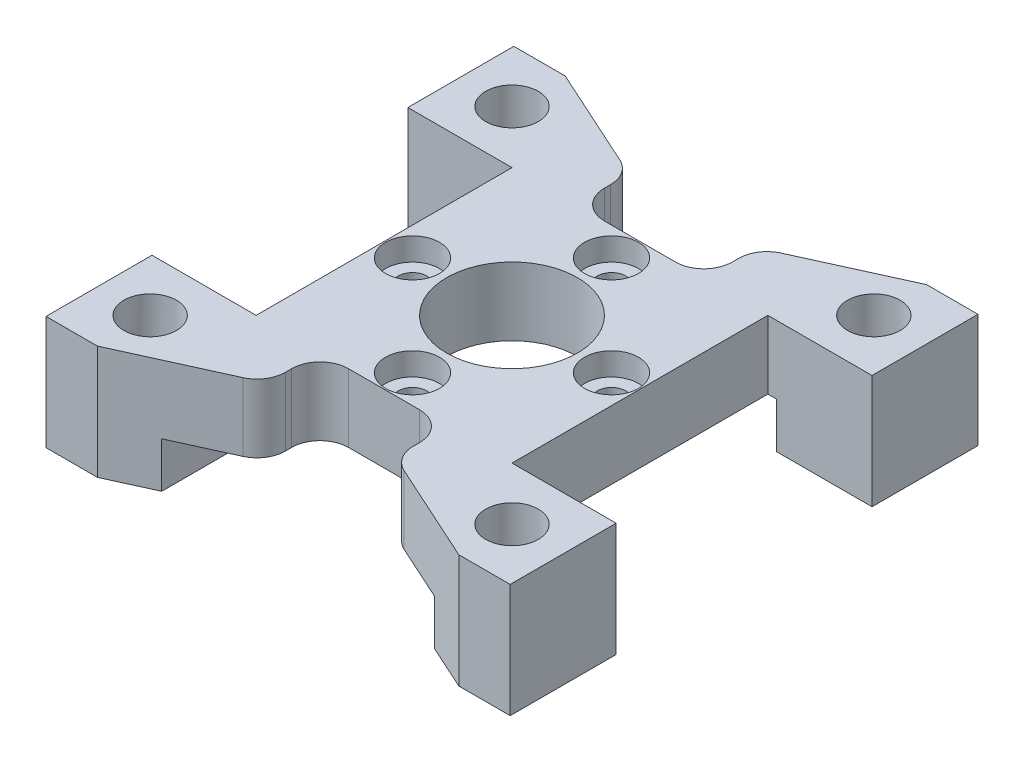
SolidWorks part; units mm, degrees
ref_plane "Front Plane" through (0, 0, 0) normal (0, 0, 1) x (1, 0, 0)
ref_plane "Top Plane" through (0, 0, 0) normal (0, 1, 0) x (1, 0, 0)
ref_plane "Right Plane" through (0, 0, 0) normal (1, 0, 0) x (0, 0, -1)
sketch "Sketch1" plane through (0, 0, 0) normal (0, 1, 0) x (1, 0, 0)
  line L0 (-31.8198, 31.8198) -> (0, 0) construction
  line L1 (-22.5, -22.5) -> (22.5, -22.5)
  line L2 (-22.5, -22.5) -> (-22.5, 22.5)
  line L3 (-22.5, 22.5) -> (22.5, 22.5)
  line L4 (22.5, -22.5) -> (22.5, 22.5)
  line L5 (-22.5, -22.5) -> (22.5, 22.5) construction
  line L6 (-22.5, 22.5) -> (22.5, -22.5) construction
  line L15 (0, 22.5) -> (0, -22.5) construction
  line L16 (0, 0) -> (31.8198, -31.8198) construction
  line L17 (-22.5, 0) -> (22.5, 0) construction
  line L18 (11.25, 22.5) -> (40.8198, 22.5)
  line L19 (11.25, 22.5) -> (11.25, 31.8198)
  line L20 (31.7885, 41.1398) -> (40.8198, 41.1398)
  line L21 (40.8198, 22.5) -> (40.8198, 41.1398)
  line L22 (0, 22.5) -> (22.5, 22.5) construction
  line L23 (11.25, 31.8198) -> (31.7885, 41.1398)
  line L24 (-40.8198, 22.5) -> (-40.8198, 41.1398)
  line L25 (-31.7885, 41.1398) -> (-40.8198, 41.1398)
  line L26 (-11.25, 31.8198) -> (-31.7885, 41.1398)
  line L27 (-11.25, 22.5) -> (-11.25, 31.8198)
  line L28 (-11.25, 22.5) -> (-40.8198, 22.5)
  line L29 (11.25, -22.5) -> (40.8198, -22.5)
  line L30 (40.8198, -22.5) -> (40.8198, -41.1398)
  line L31 (31.7885, -41.1398) -> (40.8198, -41.1398)
  line L32 (11.25, -31.8198) -> (31.7885, -41.1398)
  line L33 (11.25, -22.5) -> (11.25, -31.8198)
  line L34 (-11.25, -22.5) -> (-11.25, -31.8198)
  line L35 (-11.25, -22.5) -> (-40.8198, -22.5)
  line L36 (-40.8198, -22.5) -> (-40.8198, -41.1398)
  line L37 (-31.7885, -41.1398) -> (-40.8198, -41.1398)
  line L38 (-11.25, -31.8198) -> (-31.7885, -41.1398)
  line L44 (24, -37.6055) -> (-24, -37.6055)
  line L45 (24, -37.6055) -> (24, 37.6055)
  line L46 (24, 37.6055) -> (-24, 37.6055)
  line L47 (-24, -37.6055) -> (-24, 37.6055)
  point P0 (0, 0)
  point P6 (-31.8198, 31.8198)
  point P14 (31.8198, 31.8198)
  point P15 (31.8198, -31.8198)
  point P16 (-31.8198, -31.8198)
  point P23 (0, -37.6055)
  dimension "D9" = 1.5
  dimension "D1" = 45
  dimension "D2" = 45
  dimension "D3" = 45
  dimension "D4" = 45
  dimension "D6" = 9.32
  dimension "D7" = 9
  dimension "D8" = 8.5
  dimension "D5" = 4
extrude "Boss-Extrude1" add sketch "Sketch1" along normal blind 12 contours L3 L23 L19 | L1 L4 L3 L2 | L26 L3 L27 | L1 L38 L34 | L32 L1 L33 region at (0, 0, 0) region at (-18.1284, 0, 28.7205) region at (-18.1284, 0, -28.7205) region at (18.1284, 0, 28.7205) region at (18.1284, 0, -28.7205)
extrude "Boss-Extrude2" add sketch "Sketch1<3>" against normal blind 8 and the other way up to surface (12 mm away) contours L23 L19 L3 L18 L21 L20 | L1 L33 L32 L31 L30 L29 | L38 L34 L1 L35 L36 L37 | L28 L3 L27 L26 L25 L24 region at (-32.6768, 0, 31.4461) region at (-32.6768, 0, -31.4461) region at (32.6768, 0, 31.4461) region at (32.6768, 0, -31.4461) other way up to face at (0, 12, 0)
sketch "Sketch1<3>" plane through (0, 0, 0) normal (0, 1, 0) x (1, 0, 0) same geometry as "Sketch1"
sketch "Sketch2" plane through (0, 12, 0) normal (0, 1, 0) x (1, 0, 0)
  line L0 (0, 0) -> (-31.8198, 31.8198) construction
  line L1 (0, 22.5) -> (0, -22.5) construction
  line L4 (0, 0) -> (31.8198, -31.8198) construction
  line L5 (-22.5, 0) -> (22.5, 0) construction
  line L8 (-11.25, 22.5) -> (11.25, 22.5) construction
  line L9 (-11.25, -22.5) -> (11.25, -22.5) construction
  line L11 (22.5, -22.5) -> (22.5, 22.5) construction
  line L15 (-22.5, -22.5) -> (-22.5, 22.5) construction
  circle A0 centre (0, 0) radius 11.5
  circle A1 centre (-31.8198, 31.8198) radius 4.625
  circle A2 centre (31.8198, 31.8198) radius 4.625
  circle A3 centre (31.8198, -31.8198) radius 4.625
  circle A4 centre (-31.8198, -31.8198) radius 4.625
  circle A5 centre (0, 17.5) radius 2.5
  circle A6 centre (17.5, 0) radius 2.5
  circle A7 centre (0, -17.5) radius 2.5
  circle A8 centre (-17.5, 0) radius 2.5
  dimension "D1" = 23
  dimension "D2" = 9.25
  dimension "D6" = 5
  dimension "D3" = 45
  dimension "D4" = 45
  dimension "D7" = 5
  dimension "D5" = 4
  dimension "D8" = 4
extrude "Cut-Extrude1" cut sketch "Sketch2" against normal through all
sketch "Sketch3" plane through (0, 0, 0) normal (0, -1, 0) x (1, 0, 0)
  line L0 (31.8198, -31.8198) -> (0, 0) construction
  line L1 (0, 0) -> (-31.8198, 31.8198) construction
  circle A0 centre (31.8198, -31.8198) radius 7.625
  circle A1 centre (-31.8198, -31.8198) radius 7.625
  circle A2 centre (-31.8198, 31.8198) radius 7.625
  circle A3 centre (31.8198, 31.8198) radius 7.625
  dimension "D1" = 15.25
  dimension "D2" = 4
extrude "Cut-Extrude2" cut sketch "Sketch3" along normal through all and the other way blind 4.45
fillet "Fillet3" radius 5 8 edges at (-11.25, 6, 31.8198) (11.25, 6, 22.5) (-11.25, 6, 22.5) (11.25, 6, 31.8198) (-11.25, 6, -31.8198) (-11.25, 6, -22.5) (11.25, 6, -22.5) (11.25, 6, -31.8198)
sketch "Sketch4" plane through (0, 12, 0) normal (0, 1, 0) x (1, 0, 0)
  circle A0 centre (0, 17.5) radius 4.75
  circle A1 centre (17.5, 0) radius 4.75
  circle A2 centre (0, -17.5) radius 4.75
  circle A3 centre (-17.5, 0) radius 4.75
  circle A4 centre (17.5, 0) radius 2.5 construction
  dimension "D1" = 9.5
  dimension "D2" = 4
extrude "Cut-Extrude3" cut sketch "Sketch4" against normal blind 4
